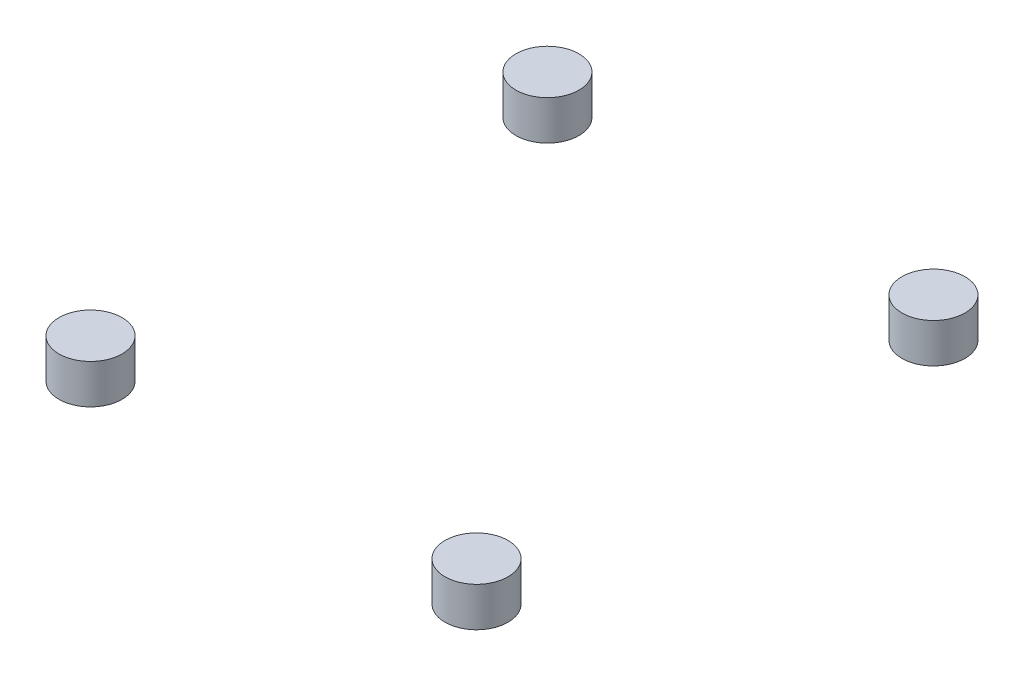
SolidWorks part; units mm, degrees
ref_plane "Front Plane" through (0, 0, 0) normal (0, 0, 1) x (1, 0, 0)
ref_plane "Top Plane" through (0, 0, 0) normal (0, 1, 0) x (1, 0, 0)
ref_plane "Right Plane" through (0, 0, 0) normal (1, 0, 0) x (0, 0, -1)
sketch "Sketch1" plane through (0, 0, 0) normal (0, 1, 0) x (1, 0, 0)
  line L0 (-24.5, 29) -> (24.5, -29) construction
  circle A0 centre (-24.5, 29) radius 4
  circle A1 centre (24.5, 29) radius 4
  circle A2 centre (24.5, -29) radius 4
  circle A3 centre (-24.5, -29) radius 4
  point P9 (0, 0)
  dimension "D3" = 8
  dimension "D1" = 49
  dimension "D2" = 58
extrude "Boss-Extrude1" add sketch "Sketch1" along normal blind 5
ref_point "Point1"
ref_point "Point2"
ref_point "Point3"
ref_axis "Axis1" through (-24.5, 5, -29) along (1, 0, 0)
